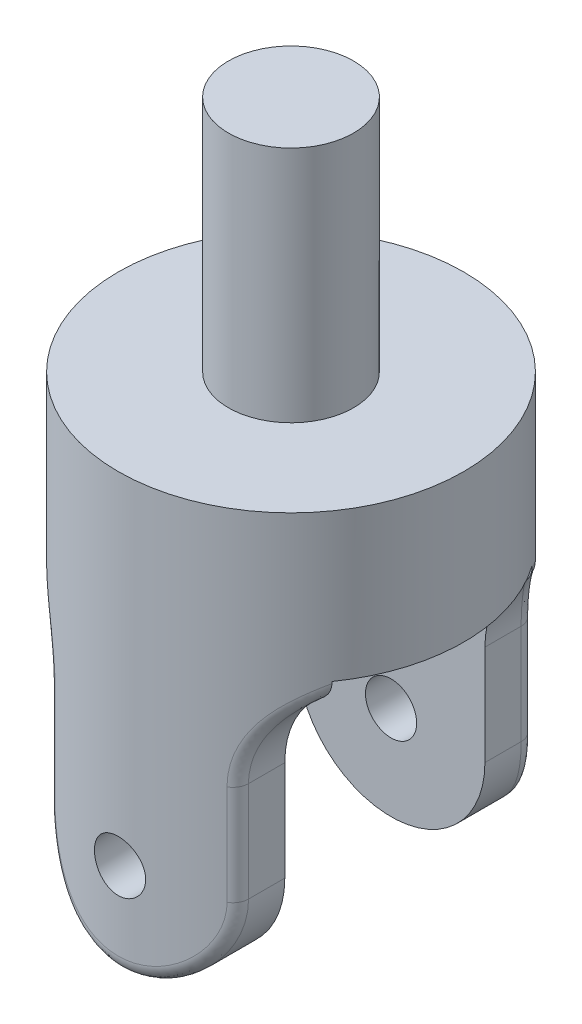
SolidWorks part; units mm, degrees
other "Markup1"
sketch "Sketch11" plane through (-17.55, 15, -20.84) normal (-0.5556, 0.8283, -0.0722) x (-0.0445, 0.0571, 0.9974)
ref_plane "Front Plane" through (0, 0, 0) normal (0, 0, 1) x (1, 0, 0)
ref_plane "Top Plane" through (0, 0, 0) normal (0, 1, 0) x (1, 0, 0)
ref_plane "Right Plane" through (0, 0, 0) normal (1, 0, 0) x (0, 0, -1)
sketch "Sketch1" plane through (0, 0, 0) normal (0, 1, 0) x (1, 0, 0)
  circle A0 centre (0, 0) radius 17.55
  dimension "D1" = 35.1
extrude "Boss-Extrude1" add sketch "Sketch1" along normal blind 15
ref_plane "Plane1" through (0, 0, 10.16) normal (0, 0, 1) x (1, 0, 0)
sketch "Sketch2" plane through (0, 0, 10.16) normal (0, 0, 1) x (1, 0, 0)
  line L0 (-9.53, -19.68) -> (-9.53, 0)
  line L1 (-17.55, 0) -> (17.55, 0) construction
  line L2 (-9.53, 0) -> (9.53, 0)
  line L3 (9.53, 0) -> (9.53, -19.68)
  circle A0 centre (0, -19.68) radius 2.6
  arc A1 (-9.53, -19.68) -> (9.53, -19.68) centre (0, -19.68) ccw
  dimension "D1" = 5.2
  dimension "D2" = 19.06
  dimension "D3" = 19.68
extrude "Boss-Extrude2" add sketch "Sketch2" along normal up to surface (7.1963 mm away) up to face at (0, 15, 17.55)
mirror "Mirror1" about plane through (0, 0, 0) normal (0, 0, 1) of "Boss-Extrude2"
fillet "Fillet1" radius 9.53 4 edges at (-9.53, 0, -12.4485) (-9.53, 0, 12.4485) (9.53, 0, -12.4485) (9.53, 0, 12.4485)
fillet "Fillet2" radius 1.6 10 edges at (9.53, -14.605, -14.7371) (-9.53, -14.605, -14.7371) (-10.7842, -4.8044, 13.8457) (-9.53, -14.605, 14.7371) (-0.4715, -29.1983, 17.5437) (9.53, -14.605, 14.7371) (-0.4715, -29.1983, -17.5437) (10.9659, -4.4994, 13.7022) (10.7842, -4.8044, -13.8457) (-10.9659, -4.4994, -13.7022)
sketch "Sketch12" plane through (0, 15, 0) normal (0, 1, 0) x (1, 0, 0)
  circle A0 centre (0, 0) radius 6.35
  dimension "D1" = 12.7
extrude "Boss-Extrude3" add sketch "Sketch12" along normal blind 24.16
